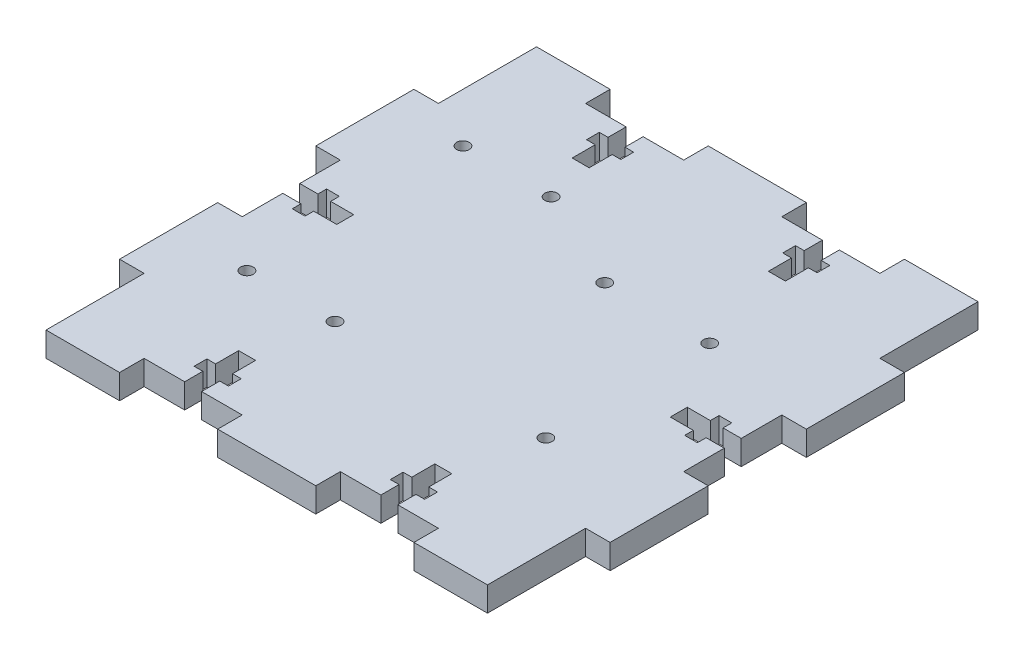
SolidWorks part; units mm, degrees
ref_plane "Front Plane" through (0, 0, 0) normal (0, 0, 1) x (1, 0, 0)
ref_plane "Top Plane" through (0, 0, 0) normal (0, 1, 0) x (1, 0, 0)
ref_plane "Right Plane" through (0, 0, 0) normal (1, 0, 0) x (0, 0, -1)
sketch "Sketch1" plane through (0, 0, 0) normal (0, 1, 0) x (1, 0, 0)
  line L1 (0, 0) -> (127, 0)
  line L2 (0, 0) -> (0, 127)
  line L3 (0, 127) -> (127, 127)
  line L4 (127, 0) -> (127, 127)
  dimension "D1" = 127
  dimension "D2" = 127
extrude "Boss-Extrude1" add sketch "Sketch1" along normal blind 6.35
sketch "Sketch2" plane through (0, 6.35, 0) normal (0, 1, 0) x (1, 0, 0)
  line L1 (0, 127) -> (6.35, 127)
  line L2 (0, 127) -> (0, 101.6)
  line L3 (0, 101.6) -> (6.35, 101.6)
  line L4 (6.35, 127) -> (6.35, 101.6)
  dimension "D1" = 25.4
  dimension "D2" = 6.35
extrude "Cut-Extrude1" cut sketch "Sketch2" against normal blind 6.35
pattern_linear "LPattern1" count 3 spacing 50.8 along (0, 0, 1) count 2 spacing 120.65 along (1, 0, 0) of "Cut-Extrude1"
sketch "Sketch3" plane through (0, 6.35, 0) normal (0, 1, 0) x (1, 0, 0)
  line L0 (6.35, 0) -> (120.65, 0) construction
  line L1 (25.4, 0) -> (50.8, 0)
  line L2 (25.4, 0) -> (25.4, 6.35)
  line L3 (25.4, 6.35) -> (50.8, 6.35)
  line L4 (50.8, 0) -> (50.8, 6.35)
  line L5 (0, 50.8) -> (0, 25.4) construction
  dimension "D1" = 25.4
  dimension "D2" = 6.35
  dimension "D3" = 25.4
extrude "Cut-Extrude2" cut sketch "Sketch3" against normal blind 6.35
pattern_linear "LPattern2" count 2 spacing 50.8 along (1, 0, 0) count 2 spacing 120.65 along (0, 0, -1) of "Cut-Extrude2"
ref_plane "Plane1" through (0, 0, -63.5) normal (0, 0, 1) x (1, 0, 0)
ref_plane "Plane2" through (63.5, 0, 0) normal (1, 0, 0) x (0, 0, -1)
sketch "Sketch4" plane through (0, 6.35, 0) normal (0, 1, 0) x (1, 0, 0)
  line L0 (120.65, 76.2) -> (120.65, 50.8) construction
  line L1 (120.65, 65.6971) -> (106.68, 65.6971)
  line L2 (120.65, 65.6971) -> (120.65, 61.3029)
  line L3 (120.65, 61.3029) -> (106.68, 61.3029)
  line L4 (106.68, 65.6971) -> (106.68, 61.3029)
  line L5 (127, 76.2) -> (120.65, 76.2) construction
  line L7 (112.649, 67.945) -> (115.951, 67.945)
  line L8 (112.649, 67.945) -> (112.649, 59.055)
  line L9 (112.649, 59.055) -> (115.951, 59.055)
  line L10 (115.951, 67.945) -> (115.951, 59.055)
  point P6 (120.65, 63.5)
  point P13 (114.3, 59.055)
  point P14 (115.951, 63.5)
  dimension "D1" = 13.97
  dimension "D2" = 4.3942
  dimension "D3" = 12.7
  dimension "D4" = 3.302
  dimension "D5" = 6.35
  dimension "D6" = 8.89
  dimension "D7" = 12.7
extrude "Cut-Extrude3" cut sketch "Sketch4" against normal blind 8.89 contours L1 L4 L3 L2 | L7 L10 L9 L8
mirror "Mirror1" about plane through (63.5, 0, 0) normal (1, 0, 0) of "Cut-Extrude3"
sketch "Sketch5" plane through (0, 6.35, 0) normal (0, 1, 0) x (1, 0, 0)
  line L0 (50.8, 6.35) -> (25.4, 6.35) construction
  line L1 (35.9029, 6.35) -> (40.2971, 6.35)
  line L2 (35.9029, 6.35) -> (35.9029, 20.32)
  line L3 (35.9029, 20.32) -> (40.2971, 20.32)
  line L4 (40.2971, 6.35) -> (40.2971, 20.32)
  line L5 (50.8, 0) -> (50.8, 6.35) construction
  line L6 (33.655, 14.351) -> (42.545, 14.351)
  line L7 (33.655, 14.351) -> (33.655, 11.049)
  line L8 (33.655, 11.049) -> (42.545, 11.049)
  line L9 (42.545, 14.351) -> (42.545, 11.049)
  point P6 (38.1, 20.32)
  point P12 (38.1, 11.049)
  point P15 (42.545, 12.7)
  dimension "D1" = 13.97
  dimension "D2" = 4.3942
  dimension "D3" = 12.7
  dimension "D4" = 3.302
  dimension "D5" = 8.89
  dimension "D6" = 12.7
  dimension "D7" = 6.35
extrude "Cut-Extrude4" cut sketch "Sketch5" against normal blind 30.48 contours L3 L4 L1 L2 | L7 L8 L9 L6
mirror "Mirror2" about plane through (63.5, 0, 0) normal (1, 0, 0) of "Cut-Extrude4"
mirror "Mirror3" about plane through (0, 0, -63.5) normal (0, 0, 1) of "Mirror2"
sketch "Sketch10" plane through (0, 6.35, 0) normal (0, 1, 0) x (1, 0, 0)
  line L0 (0, 101.6) -> (0, 76.2) construction
  line L1 (19.05, 95.25) -> (41.8592, 95.25)
  line L2 (19.05, 95.25) -> (19.05, 39.3192)
  line L3 (19.05, 39.3192) -> (41.8592, 39.3192)
  line L4 (41.8592, 95.25) -> (41.8592, 39.3192)
  line L5 (127, 120.65) -> (152.4, 120.65) construction
  point P6 (0, 88.9)
  dimension "D1" = 22.8092
  dimension "D2" = 55.9308
  dimension "D4" = 19.05
  dimension "D5" = 25.4
hole_wizard "#4 Clearance Hole2" positions "Sketch12" profile "Sketch11" hole size "#4" standard "ANSI Inch"
sketch "Sketch12" plane through (0, 6.35, 0) normal (0, 1, 0) x (1, 0, 0)
  point P0 (19.05, 95.25)
  point P3 (41.8592, 95.25)
  point P6 (41.8592, 39.3192)
  point P9 (19.05, 39.3192)
sketch "Sketch11" plane through (19.05, 6.35, -95.25) normal (1, 0, 0) x (0, 0, 1)
  line L0 (0, 0) -> (0, 11.1406)
  line L1 (0, 11.1406) -> (1.6319, 10.16)
  line L2 (1.6319, 10.16) -> (1.6319, 0)
  line L5 (1.6319, 0) -> (0, 0)
  line L10 (0, 11.1406) -> (-1.6319, 10.16) construction
  line L11 (0, -6.35) -> (0, 107.95) construction
  dimension "Hole Dia." = 3.2639
  dimension "Hole Depth" = 10.16
  dimension "Drill Angle" = 118
sketch "Sketch13" plane through (0, 6.35, 0) normal (0, 1, 0) x (1, 0, 0)
  line L0 (106.68, 65.6971) -> (106.68, 61.3029) construction
  line L1 (57.15, 90.551) -> (107.95, 90.551)
  line L2 (57.15, 90.551) -> (57.15, 36.449)
  line L3 (57.15, 36.449) -> (107.95, 36.449)
  line L4 (107.95, 90.551) -> (107.95, 36.449)
  line L5 (57.15, 90.551) -> (107.95, 36.449) construction
  line L6 (57.15, 36.449) -> (107.95, 90.551) construction
  line L7 (127, 76.2) -> (127, 101.6) construction
  point P0 (82.55, 63.5)
  point P7 (106.68, 63.5)
  dimension "D1" = 50.8
  dimension "D2" = 54.102
  dimension "D3" = 19.05
hole_wizard "#4 Clearance Hole3" positions "Sketch15" profile "Sketch14" hole size "#4" standard "ANSI Inch"
sketch "Sketch15" plane through (0, 6.35, 0) normal (0, 1, 0) x (1, 0, 0)
  line L0 (57.15, 90.551) -> (107.95, 90.551) construction
  line L3 (57.15, 90.551) -> (57.15, 36.449) construction
  point P0 (68.072, 82.931)
  point P2 (95.25, 82.931)
  point P4 (95.25, 40.513)
  dimension "D1" = 7.62
  dimension "D2" = 10.922
  dimension "D3" = 27.178
  dimension "D4" = 42.418
sketch "Sketch14" plane through (68.072, 6.35, -82.931) normal (1, 0, 0) x (0, 0, 1)
  line L0 (0, 0) -> (0, 11.1406)
  line L1 (0, 11.1406) -> (1.6319, 10.16)
  line L2 (1.6319, 10.16) -> (1.6319, 0)
  line L5 (1.6319, 0) -> (0, 0)
  line L10 (0, 11.1406) -> (-1.632, 10.16) construction
  line L11 (0, -6.35) -> (0, 107.95) construction
  dimension "Hole Dia." = 3.2639
  dimension "Hole Depth" = 10.16
  dimension "Drill Angle" = 118
